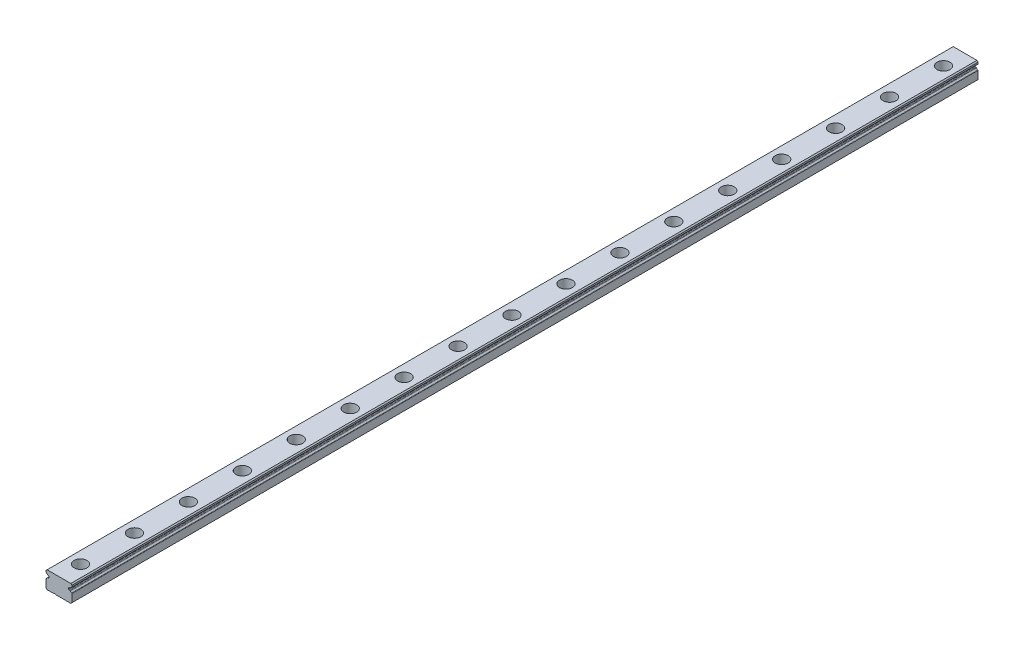
SolidWorks part; units mm, degrees
ref_plane "Front Plane" through (0, 0, 0) normal (0, 0, 1) x (1, 0, 0)
ref_plane "Top Plane" through (0, 0, 0) normal (0, 1, 0) x (1, 0, 0)
ref_plane "Right Plane" through (0, 0, 0) normal (1, 0, 0) x (0, 0, -1)
sketch "Sketch1" plane through (0, 0, 0) normal (0, 0, 1) x (1, 0, 0)
  line B0 (5.5, -8) -> (6, -7.5)
  line B1 (6, -7.5) -> (6, -3.8579)
  line B2 (5.0738, -3.0055) -> (4.7282, -2.9753)
  line B3 (4.5, -2.7262) -> (4.5, -2.2738)
  line B4 (4.7282, -2.0247) -> (5.0948, -1.9927)
  line B5 (6, -1.1746) -> (6, -0.5)
  line B6 (6, -0.5) -> (5.5, 0)
  line B7 (5.5, 0) -> (-5.5, 0)
  line B8 (-5.5, 0) -> (-6, -0.5)
  line B9 (-6, -0.5) -> (-6, -1.1746)
  line B10 (-5.0948, -1.9927) -> (-4.7282, -2.0247)
  line B11 (-4.5, -2.2738) -> (-4.5, -2.7262)
  line B12 (-4.7282, -2.9753) -> (-5.0738, -3.0055)
  line B13 (-6, -3.8579) -> (-6, -7.5)
  line B14 (-6, -7.5) -> (-5.5, -8)
  line B15 (-5.5, -8) -> (-2.4, -8)
  line B16 (-1.6, -8) -> (5.5, -8)
  line B17 (0, 0) -> (0, -8) construction
  arc B18 (6, -3.8579) -> (5.8448, -3.6266) centre (5.75, -3.8579) ccw
  arc B19 (5.2672, -3.1272) -> (5.8448, -3.6266) centre (6.3, -2.5162) ccw
  arc B20 (5.2672, -3.1272) -> (5.0738, -3.0055) centre (5.052, -3.2545) ccw
  arc B21 (4.5, -2.7262) -> (4.7282, -2.9753) centre (4.75, -2.7262) ccw
  arc B22 (4.7282, -2.0247) -> (4.5, -2.2738) centre (4.75, -2.2738) ccw
  arc B23 (5.0948, -1.9927) -> (5.2845, -1.8768) centre (5.073, -1.7436) ccw
  arc B24 (5.8448, -1.4059) -> (5.2845, -1.8768) centre (6.3, -2.5162) ccw
  arc B25 (5.8448, -1.4059) -> (6, -1.1746) centre (5.75, -1.1746) ccw
  arc B26 (-6, -1.1746) -> (-5.8448, -1.4059) centre (-5.75, -1.1746) ccw
  arc B27 (-5.2845, -1.8768) -> (-5.8448, -1.4059) centre (-6.3, -2.5162) ccw
  arc B28 (-5.2845, -1.8768) -> (-5.0948, -1.9927) centre (-5.073, -1.7436) ccw
  arc B29 (-4.5, -2.2738) -> (-4.7282, -2.0247) centre (-4.75, -2.2738) ccw
  arc B30 (-4.7282, -2.9753) -> (-4.5, -2.7262) centre (-4.75, -2.7262) ccw
  arc B31 (-5.0738, -3.0055) -> (-5.2672, -3.1272) centre (-5.052, -3.2545) ccw
  arc B32 (-5.8448, -3.6266) -> (-5.2672, -3.1272) centre (-6.3, -2.5162) ccw
  arc B33 (-5.8448, -3.6266) -> (-6, -3.8579) centre (-5.75, -3.8579) ccw
  arc B34 (-1.6, -8) -> (-2.4, -8) centre (-2, -8.3) ccw
sketch_block_instance "Block1-1"
sketch_block "Block1"
extrude "Boss-Extrude1" add sketch "Sketch1" along normal blind 420
sketch "Sketch2" plane through (0, 0, 0) normal (0, 1, 0) x (1, 0, 0)
  line L0 (0, 0) -> (0, -420) construction
  line L1 (5.5, 0) -> (-5.5, 0) construction
  line L2 (-5.5, -420) -> (5.5, -420) construction
  line L3 (5.5, -420) -> (-5.5, -420) construction
  circle A0 centre (0, -10) radius 3
  circle A1 centre (0, -10) radius 1.75
  circle A2 centre (0, -35) radius 3
  circle A3 centre (0, -35) radius 1.75
  circle A4 centre (0, -60) radius 3
  circle A5 centre (0, -60) radius 1.75
  circle A6 centre (0, -85) radius 3
  circle A7 centre (0, -85) radius 1.75
  circle A8 centre (0, -110) radius 3
  circle A9 centre (0, -110) radius 1.75
  circle A10 centre (0, -135) radius 3
  circle A11 centre (0, -135) radius 1.75
  circle A12 centre (0, -160) radius 3
  circle A13 centre (0, -160) radius 1.75
  circle A14 centre (0, -185) radius 3
  circle A15 centre (0, -185) radius 1.75
  circle A16 centre (0, -210) radius 3
  circle A17 centre (0, -210) radius 1.75
  circle A18 centre (0, -235) radius 3
  circle A19 centre (0, -235) radius 1.75
  circle A20 centre (0, -260) radius 3
  circle A21 centre (0, -260) radius 1.75
  circle A22 centre (0, -285) radius 3
  circle A23 centre (0, -285) radius 1.75
  circle A24 centre (0, -310) radius 3
  circle A25 centre (0, -310) radius 1.75
  circle A26 centre (0, -335) radius 3
  circle A27 centre (0, -335) radius 1.75
  circle A28 centre (0, -360) radius 3
  circle A29 centre (0, -360) radius 1.75
  circle A30 centre (0, -385) radius 3
  circle A31 centre (0, -385) radius 1.75
  circle A32 centre (0, -410) radius 3
  circle A33 centre (0, -410) radius 1.75
  dimension "D1" = 10
  dimension "D2" = 3.5
  dimension "D3" = 6
  dimension "D5" = 25
  dimension "D6" = 135
  dimension "D4" = 17
extrude "Cut-Extrude1" cut sketch "Sketch2" against normal through all contours A1 | A3 | A5 | A7 | A9 | A11 | A13 | A15 | A17 | A19 | A21 | A23 | A25 | A27 | A29 | A31 | A33
extrude "Cut-Extrude2" cut sketch "Sketch2<3>" against normal blind 4.5 contours A0 | A2 | A4 | A6 | A8 | A10 | A12 | A14 | A16 | A18 | A20 | A22 | A24 | A26 | A28 | A30 | A32
sketch "Sketch2<3>" plane through (0, 0, 0) normal (0, 1, 0) x (1, 0, 0) same geometry as "Sketch2"
ref_plane "Groove Center" through (0, -2.5, 0) normal (0, -1, 0) x (-1, 0, 0)
ref_plane "Rail Center" through (0, 0, 0) normal (-1, 0, 0) x (0, 0, 1)
ref_plane "Rail Mid Length Plane" through (0, 0, 210) normal (0, 0, 1) x (1, 0, 0)
